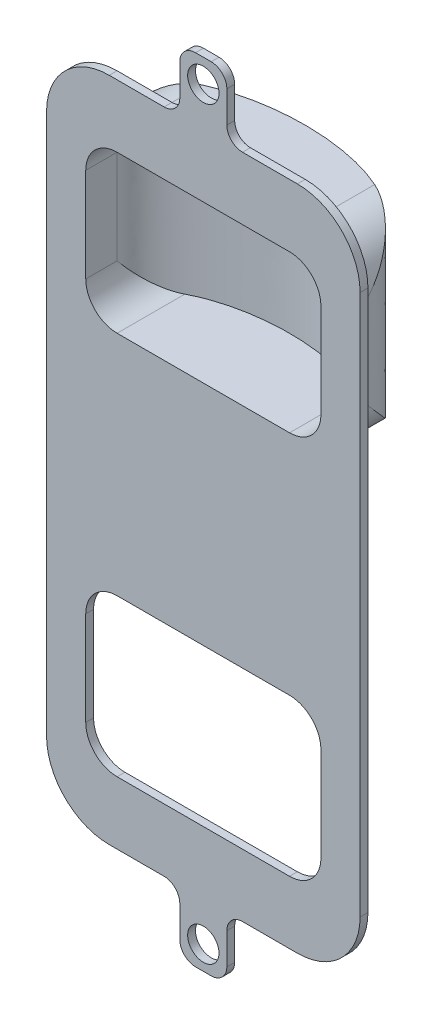
SolidWorks part; units mm, degrees
ref_plane "Front Plane" through (0, 0, 0) normal (0, 0, 1) x (1, 0, 0)
ref_plane "Top Plane" through (0, 0, 0) normal (0, 1, 0) x (1, 0, 0)
ref_plane "Right Plane" through (0, 0, 0) normal (1, 0, 0) x (0, 0, -1)
sketch "Sketch1" plane through (0, 0, 0) normal (0, 0, 1) x (1, 0, 0)
  line L0 (0, 24.5) -> (-90.5909, 24.5) construction
  line L1 (-11, -10) -> (11, -10)
  line L2 (-15, -6) -> (-15, 6)
  line L3 (-11, 10) -> (11, 10)
  line L4 (15, -6) -> (15, 6)
  line L5 (-15, -10) -> (15, 10) construction
  line L6 (-15, 10) -> (15, -10) construction
  line L7 (-20, 59) -> (-20, -10)
  line L8 (-12, -18) -> (-5, -18)
  line L9 (20, -10) -> (20, 59)
  line L10 (-3, -20) -> (-3, -24)
  line L11 (-1, -26) -> (1, -26)
  line L12 (3, -24) -> (3, -20)
  line L13 (5, -18) -> (12, -18)
  line L14 (-15, 39) -> (15, 59) construction
  line L15 (-15, 59) -> (15, 39) construction
  line L16 (5, 67) -> (12, 67)
  line L17 (3, 73) -> (3, 69)
  line L18 (-1, 75) -> (1, 75)
  line L19 (-3, 69) -> (-3, 73)
  line L20 (-12, 67) -> (-5, 67)
  line L21 (15, 55) -> (15, 43)
  line L22 (-11, 39) -> (11, 39)
  line L23 (-15, 55) -> (-15, 43)
  line L24 (-11, 59) -> (11, 59)
  circle A0 centre (0, -23) radius 2
  arc A1 (-11, -10) -> (-15, -6) centre (-11, -6) cw
  arc A2 (11, -10) -> (15, -6) centre (11, -6) ccw
  arc A3 (11, 10) -> (15, 6) centre (11, 6) cw
  arc A4 (-15, 6) -> (-11, 10) centre (-11, 6) cw
  arc A5 (1, -26) -> (3, -24) centre (1, -24) ccw
  arc A6 (-3, -24) -> (-1, -26) centre (-1, -24) ccw
  arc A7 (3, -20) -> (5, -18) centre (5, -20) cw
  arc A8 (-3, -20) -> (-5, -18) centre (-5, -20) ccw
  arc A9 (12, -18) -> (20, -10) centre (12, -10) ccw
  arc A10 (-20, -10) -> (-12, -18) centre (-12, -10) ccw
  arc A11 (-20, 59) -> (-12, 67) centre (-12, 59) cw
  arc A12 (12, 67) -> (20, 59) centre (12, 59) cw
  arc A13 (-3, 69) -> (-5, 67) centre (-5, 69) cw
  arc A14 (3, 69) -> (5, 67) centre (5, 69) ccw
  arc A15 (-3, 73) -> (-1, 75) centre (-1, 73) cw
  arc A16 (1, 75) -> (3, 73) centre (1, 73) cw
  arc A17 (-15, 43) -> (-11, 39) centre (-11, 43) ccw
  arc A18 (11, 39) -> (15, 43) centre (11, 43) ccw
  arc A19 (11, 59) -> (15, 55) centre (11, 55) cw
  arc A20 (-11, 59) -> (-15, 55) centre (-11, 55) ccw
  circle A21 centre (0, 72) radius 2
  point P0 (0, 0)
  point P23 (3, 67)
  point P26 (-20, 24.5)
  point P28 (0, -26)
  point P37 (3, -18)
  point P80 (20, 24.5)
  point P81 (0, 49)
  dimension "D6" = 4
  dimension "D5" = 4
  dimension "D12" = 2
  dimension "D13" = 2
  dimension "D14" = 8
  dimension "D1" = 30
  dimension "D2" = 20
  dimension "D3" = 23
  dimension "D4" = 95
  dimension "D7" = 5
  dimension "D8" = 5
  dimension "D9" = 5
  dimension "D10" = 3
  dimension "D11" = 6
extrude "Boss-Extrude1" add sketch "Sketch1" along normal blind 1
sketch "Sketch3" plane through (0, 0, 0) normal (0, 0, -1) x (-1, 0, 0)
  line L0 (15, 55) -> (15, 43) construction
  line L1 (17, 55) -> (17, 43)
  line L2 (-11, 59) -> (11, 59) construction
  line L3 (-15, 43) -> (-15, 55) construction
  line L4 (11, 39) -> (-11, 39) construction
  line L5 (15, 55) -> (15, 43)
  line L6 (-11, 59) -> (11, 59)
  line L7 (-15, 43) -> (-15, 55)
  line L8 (11, 39) -> (-11, 39)
  line L9 (11, 37) -> (-11, 37)
  line L10 (-17, 43) -> (-17, 55)
  line L11 (-11, 61) -> (11, 61)
  arc A0 (11, 37) -> (17, 43) centre (11, 43) ccw
  arc A1 (-17, 43) -> (-11, 37) centre (-11, 43) ccw
  arc A2 (11, 39) -> (15, 43) centre (11, 43) ccw construction
  arc A3 (15, 55) -> (11, 59) centre (11, 55) ccw construction
  arc A4 (-11, 59) -> (-15, 55) centre (-11, 55) ccw construction
  arc A5 (-15, 43) -> (-11, 39) centre (-11, 43) ccw construction
  arc A6 (11, 39) -> (15, 43) centre (11, 43) ccw
  arc A7 (15, 55) -> (11, 59) centre (11, 55) ccw
  arc A8 (-11, 59) -> (-15, 55) centre (-11, 55) ccw
  arc A9 (-15, 43) -> (-11, 39) centre (-11, 43) ccw
  arc A10 (-11, 61) -> (-17, 55) centre (-11, 55) ccw
  arc A11 (17, 55) -> (11, 61) centre (11, 55) ccw
  arc M34 (15, 43) -> (11, 39) centre (11, 43) cw
  line M35 (11, 39) -> (-11, 39)
  arc M36 (-11, 39) -> (-15, 43) centre (-11, 43) cw
  line M37 (-15, 43) -> (-15, 55)
  arc M38 (-15, 55) -> (-11, 59) centre (-11, 55) cw
  line M39 (-11, 59) -> (11, 59)
  arc M40 (11, 59) -> (15, 55) centre (11, 55) cw
  line M41 (15, 55) -> (15, 43)
  dimension "D1" = 2
extrude "Boss-Extrude2" add sketch "Sketch3" along normal blind 12 separate body contours M34 M41 M40 M39 M38 M37 M36 M35 | L1 A11 L11 A10 L10 A1 L9 A0 M41 M34 M35 M36 M37 M38 M39 M40 region at (-16.5838, 49, 0) region at (0, 49, 0)
sketch "Sketch4" plane through (0, 0, 0) normal (0, 1, 0) x (1, 0, 0)
  line L0 (-11, 12) -> (11, 12) construction
  line L1 (-17, 12) -> (-17, 0) construction
  line L2 (-17, 3) -> (-17, 21.8646)
  line L3 (-17, 21.8646) -> (17, 21.8646)
  line L4 (17, 21.8646) -> (17, 3)
  line L5 (-19, 3) -> (-19, 23.8646)
  line L6 (-19, 23.8646) -> (19, 23.8646)
  line L7 (19, 23.8646) -> (19, 3)
  line L8 (-17, 3) -> (-19, 3)
  line L9 (17, 3) -> (19, 3)
  ellipse E0 centre (0, 3) end of major axis (17, 3) minor radius 9
  dimension "D1" = 3
  dimension "D2" = 2
extrude "Cut-Extrude5" cut sketch "Sketch4" along normal through all both and the other way through all contours E0 L4 L3 L2 | L4 L9 L7 L6 L5 L8 L2 L3 | L3 L4 L9 L7 L6 L5 L8 L2 region at (-18, 0, -3.4335) region at (0, 0, -15.7955)
shell "Shell1" thickness 2 removed face at (0, 49, 0)
combine bodies "Combine1" operation type add bodies to combine 101 103
